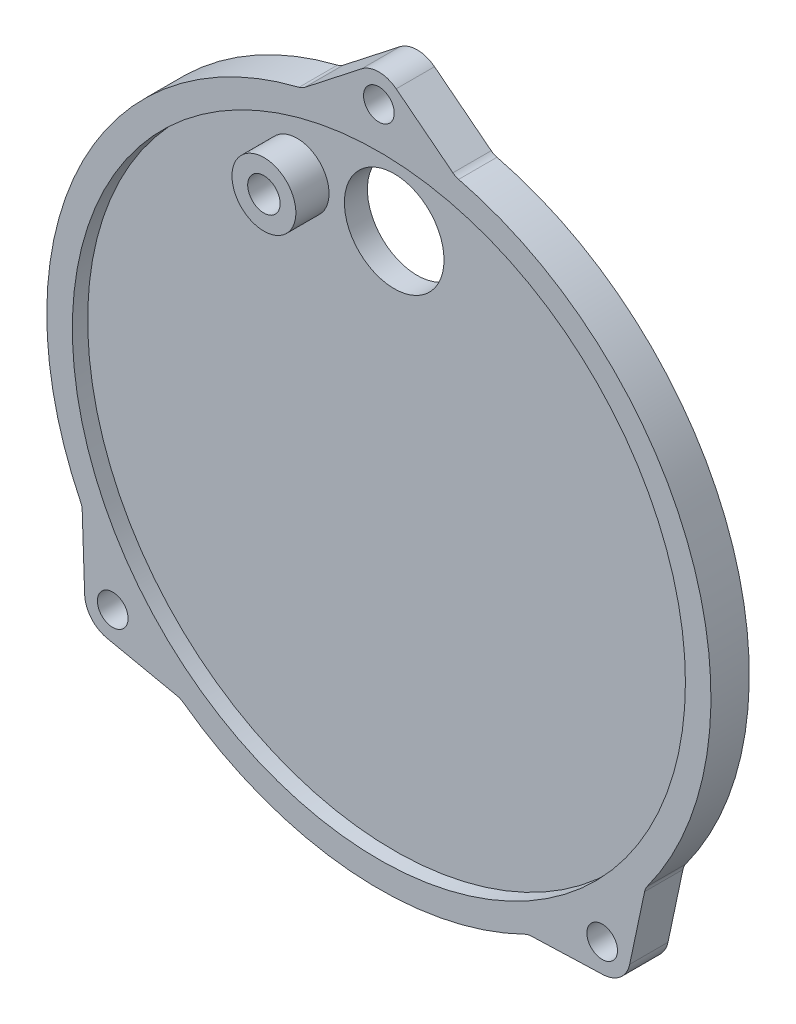
SolidWorks part; units mm, degrees
ref_plane "Front Plane" through (0, 0, 0) normal (0, 0, 1) x (1, 0, 0)
ref_plane "Top Plane" through (0, 0, 0) normal (0, 1, 0) x (1, 0, 0)
ref_plane "Right Plane" through (0, 0, 0) normal (1, 0, 0) x (0, 0, -1)
sketch "Sketch1" plane through (0, 0, 0) normal (0, 0, 1) x (1, 0, 0)
  circle A0 centre (0, 0) radius 65
  dimension "D1" = 130
extrude "Boss-Extrude1" add sketch "Sketch1" along normal blind 4.5
sketch "Sketch2" plane through (0, 0, 4.5) normal (0, 0, 1) x (1, 0, 0)
  line L0 (0, 68) -> (0, 0) construction
  line L1 (0, 0) -> (-52.091, -43.7096) construction
  line L2 (0, 0) -> (43.7096, -52.091) construction
  circle A0 centre (43.7096, -52.091) radius 3
  circle A1 centre (0, 68) radius 3
  circle A2 centre (-52.091, -43.7096) radius 3
  circle A3 centre (0, 0) radius 68 construction
  dimension "D1" = 6
  dimension "D2" = 136
  dimension "D3" = 130
  dimension "D4" = 140
sketch "Sketch3" plane through (0, 0, 4.5) normal (0, 0, 1) x (1, 0, 0)
  line L0 (-19, 45) -> (0, 45) construction
  line L1 (0, 45) -> (0, 0) construction
  circle A0 centre (0, 45) radius 9.75
  circle A1 centre (-19, 45) radius 3.175
  dimension "D1" = 6.35
  dimension "D2" = 19.5
  dimension "D3" = 19
  dimension "D4" = 45
extrude "Cut-Extrude2" cut sketch "Sketch3" against normal up to surface (4.5 mm away) up to face at (65, 0, 0)
sketch "Sketch4" plane through (0, 0, 0) normal (0, 0, 1) x (1, 0, 0)
  line L2 (-57.5878, -43.8972) -> (-58.0907, -29.1628)
  line L3 (-53.2303, -49.0903) -> (-38.8071, -52.1441)
  line L4 (49.0903, -53.2303) -> (52.1441, -38.8071)
  line L5 (43.8972, -57.5878) -> (29.1628, -58.0907)
  line L6 (-3.3896, 72.3314) -> (-15, 63.2456)
  line L7 (3.3896, 72.3314) -> (15, 63.2456)
  circle A0 centre (0, 0) radius 60
  arc A1 (-15, 63.2456) -> (-58.0907, -29.1628) centre (0, 0) ccw
  arc A2 (3.3896, 72.3314) -> (-3.3896, 72.3314) centre (0, 68) ccw
  arc A3 (43.8972, -57.5878) -> (49.0903, -53.2303) centre (43.7096, -52.091) ccw
  arc A4 (-57.5878, -43.8972) -> (-53.2303, -49.0903) centre (-52.091, -43.7096) ccw
  arc A6 (-38.8071, -52.1441) -> (29.1628, -58.0907) centre (0, 0) ccw
  arc A7 (52.1441, -38.8071) -> (15, 63.2456) centre (0, 0) ccw
  circle A8 centre (-52.091, -43.7096) radius 3
  circle A9 centre (43.7096, -52.091) radius 3
  circle A10 centre (0, 68) radius 3
  circle A11 centre (-52.091, -43.7096) radius 3 construction
  dimension "D1" = 120
  dimension "D2" = 130
  dimension "D3" = 11
  dimension "D4" = 30
  dimension "D5" = 30
  dimension "D6" = 30
extrude "Boss-Extrude2" add sketch "Sketch4" along normal blind 7.5
fillet "Fillet1" radius 3 6 edges at (52.1441, -38.8071, 3.75) (29.1628, -58.0907, 3.75) (-38.8071, -52.1441, 3.75) (-58.0907, -29.1628, 3.75) (-15, 63.2456, 3.75) (15, 63.2456, 3.75)
sketch "Sketch6" plane through (0, 0, 4.5) normal (0, 0, 1) x (1, 0, 0)
  circle A0 centre (-19, 45) radius 6.25
  circle A1 centre (-19, 45) radius 3.175
  circle A2 centre (-19, 45) radius 3.175 construction
  dimension "D1" = 12.5
extrude "Boss-Extrude3" add sketch "Sketch6" along normal blind 6.5
